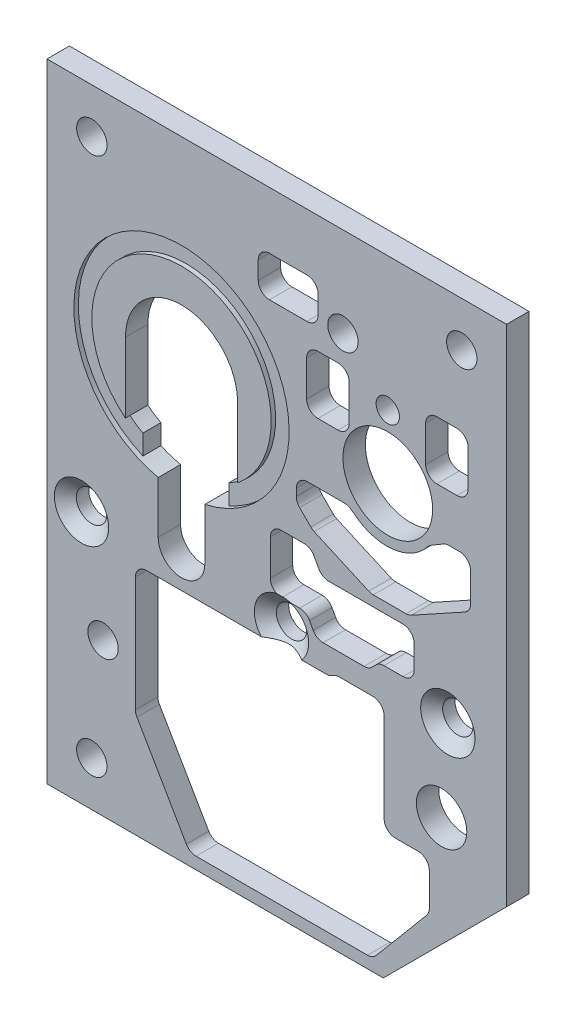
SolidWorks part; units mm, degrees
material "Acrylic (Medium-high impact)"
ref_plane "Front Plane" through (0, 0, 0) normal (0, 0, 1) x (1, 0, 0)
ref_plane "Top Plane" through (0, 0, 0) normal (0, 1, 0) x (1, 0, 0)
ref_plane "Right Plane" through (0, 0, 0) normal (1, 0, 0) x (0, 0, -1)
sketch "Sketch1" plane through (0, 0, 0) normal (0, 0, 1) x (1, 0, 0)
  line L5 (-65.0875, 0) -> (-65.0875, -88.9)
  line L6 (-65.0875, -88.9) -> (-17.4625, -88.9)
  line L7 (-17.4625, -88.9) -> (0, -71.4375)
  line L8 (0, -71.4375) -> (0, 0)
  line L9 (0, 0) -> (-65.0875, 0)
  line L10 (-65.0875, 0) -> (-65.0875, -88.9)
  line L11 (-65.0875, -88.9) -> (-17.4625, -88.9)
  line L12 (-17.4625, -88.9) -> (0, -71.4375)
  line L13 (0, -71.4375) -> (0, 0)
  line L14 (0, 0) -> (-65.0875, 0)
  dimension "D1" = 0
extrude "Boss-Extrude1" add sketch "Sketch1" against normal blind 3.175
hole_wizard "#6 Clearance Hole1" positions "Sketch3" profile "Sketch2" hole size "#6" standard "ANSI Inch" end condition through all
sketch "Sketch3" plane through (0, 0, 0) normal (0, 0, 1) x (1, 0, 0)
  point P0 (-58.7375, -6.35)
  point P3 (-6.35, -6.35)
  point P6 (-23.1775, -12.7)
  point P9 (-57.15, -67.31)
  point P12 (-58.7375, -82.55)
sketch "Sketch2" plane through (-58.7375, -6.35, 0) normal (1, 0, 0) x (0, -1, 0)
  line L0 (0, 0) -> (0, 3.175)
  line L1 (0, 3.175) -> (2.1526, 3.175)
  line L2 (2.1526, 3.175) -> (2.1526, 0)
  line L5 (2.1526, 0) -> (0, 0)
  line L11 (0, -6.35) -> (0, 107.95) construction
  dimension "Thru Hole Dia." = 4.3053
  dimension "Thru Hole Depth" = 3.175
sketch "Sketch4" plane through (0, 0, 0) normal (0, 0, 1) x (1, 0, 0)
  line L0 (-49.3395, -50.8) -> (-49.3395, -43.453) construction
  line L1 (-42.7355, -43.453) -> (-42.7355, -50.8) construction
  line L2 (-49.3395, -50.8) -> (-49.3395, -43.453)
  line L3 (-42.7355, -43.453) -> (-42.7355, -50.8)
  arc A0 (-42.7355, -43.453) -> (-49.3395, -43.453) centre (-46.0375, -28.575) ccw construction
  arc A1 (-49.3395, -50.8) -> (-42.7355, -50.8) centre (-46.0375, -50.8) ccw construction
  arc A2 (-42.7355, -43.453) -> (-49.3395, -43.453) centre (-46.0375, -28.575) ccw
  arc A3 (-49.3395, -50.8) -> (-42.7355, -50.8) centre (-46.0375, -50.8) ccw
extrude "Cut-Extrude1" cut sketch "Sketch4" against normal through all
sketch "Sketch5" plane through (0, 0, 0) normal (0, 0, 1) x (1, 0, 0)
  circle A0 centre (-16.8275, -27.94) radius 6.35
  circle A1 centre (-16.8275, -18.9484) radius 1.651
  dimension "D1" = 12.7
  dimension "D2" = 3.302
  dimension "D3" = 8.9916
extrude "Cut-Extrude2" cut sketch "Sketch5" against normal through all
hole_wizard "1/4 Clearance Hole1" positions "Sketch7" profile "Sketch6" hole size "1/4" standard "ANSI Inch" end condition through all
sketch "Sketch7" plane through (0, 0, 0) normal (0, 0, 1) x (1, 0, 0)
  point P0 (-9.2075, -65.0875)
sketch "Sketch6" plane through (-9.2075, -65.0875, 0) normal (1, 0, 0) x (0, -1, 0)
  line L0 (0, 0) -> (0, 3.175)
  line L1 (0, 3.175) -> (3.5712, 3.175)
  line L2 (3.5712, 3.175) -> (3.5712, 0)
  line L5 (3.5712, 0) -> (0, 0)
  line L11 (0, -6.35) -> (0, 107.95) construction
  dimension "Thru Hole Dia." = 7.1425
  dimension "Thru Hole Depth" = 3.175
sketch "Sketch8" plane through (0, 0, -3.175) normal (0, 0, -1) x (-1, 0, 0)
  line L0 (52.1335, -39.7163) -> (52.1335, -42.5427) construction
  line L1 (53.975, -28.575) -> (53.975, -38.4889) construction
  line L2 (38.1, -38.4889) -> (38.1, -28.575) construction
  line L3 (39.9415, -42.5427) -> (39.9415, -39.7163) construction
  line L4 (52.1335, -39.7163) -> (52.1335, -42.5427)
  line L5 (53.975, -28.575) -> (53.975, -38.4889)
  line L6 (38.1, -38.4889) -> (38.1, -28.575)
  line L7 (39.9415, -42.5427) -> (39.9415, -39.7163)
  arc A0 (52.1335, -39.7163) -> (53.975, -38.4889) centre (46.0375, -28.575) ccw construction
  arc A1 (53.975, -28.575) -> (38.1, -28.575) centre (46.0375, -28.575) ccw construction
  arc A2 (38.1, -38.4889) -> (39.9415, -39.7163) centre (46.0375, -28.575) ccw construction
  arc A3 (49.3395, -43.453) -> (42.7355, -43.453) centre (46.0375, -28.575) ccw construction
  arc A4 (52.1335, -39.7163) -> (53.975, -38.4889) centre (46.0375, -28.575) ccw
  arc A5 (53.975, -28.575) -> (38.1, -28.575) centre (46.0375, -28.575) ccw
  arc A6 (38.1, -38.4889) -> (39.9415, -39.7163) centre (46.0375, -28.575) ccw
  arc A7 (52.1335, -42.5427) -> (39.9415, -42.5427) centre (46.0375, -28.575) ccw
extrude "Boss-Extrude2" add sketch "Sketch8" against normal through all
sketch "Sketch9" plane through (0, 0, 0) normal (0, 0, 1) x (1, 0, 0)
  line L0 (-52.1335, -39.7163) -> (-52.1335, -42.5427) construction
  line L1 (-39.9415, -42.5427) -> (-39.9415, -39.7163) construction
  line L2 (-52.1335, -39.7163) -> (-52.1335, -42.5427)
  line L3 (-39.9415, -42.5427) -> (-39.9415, -39.7163)
  arc A0 (-42.7355, -43.453) -> (-49.3395, -43.453) centre (-46.0375, -28.575) ccw construction
  arc A1 (-53.975, -38.4889) -> (-52.1335, -39.7163) centre (-46.0375, -28.575) ccw construction
  arc A2 (-38.1, -38.4889) -> (-53.975, -38.4889) centre (-46.0375, -28.575) ccw construction
  arc A3 (-39.9415, -39.7163) -> (-38.1, -38.4889) centre (-46.0375, -28.575) ccw construction
  arc A4 (-39.9415, -42.5427) -> (-52.1335, -42.5427) centre (-46.0375, -28.575) ccw
  arc A5 (-53.975, -38.4889) -> (-52.1335, -39.7163) centre (-46.0375, -28.575) ccw
  arc A6 (-38.1, -38.4889) -> (-53.975, -38.4889) centre (-46.0375, -28.575) ccw
  arc A7 (-39.9415, -39.7163) -> (-38.1, -38.4889) centre (-46.0375, -28.575) ccw
extrude "Cut-Extrude3" cut sketch "Sketch9" against normal blind 0.635
hole_wizard "CSK for #6 Flat Head Machine Screw (100)1" positions "Sketch11" profile "Sketch10" countersink size "#6" standard "ANSI Inch" end condition through all
sketch "Sketch11" plane through (0, 0, 0) normal (0, 0, 1) x (1, 0, 0)
  point P1 (-31.877, -53.0919)
  point P5 (-60.198, -53.0919)
  point P8 (-8.321, -53.0919)
sketch "Sketch10" plane through (-31.877, -53.0919, 0) normal (1, 0, 0) x (0, -1, 0)
  line L0 (0, 0) -> (0, 3.175)
  line L1 (0, 3.175) -> (2.1526, 3.175)
  line L2 (2.1526, 3.175) -> (2.1526, 1.4209)
  line L3 (2.1526, 1.4209) -> (3.846, 0)
  line L5 (3.846, 0) -> (0, 0)
  line L6 (-2.1526, 1.4209) -> (-3.846, 0) construction
  line L11 (0, -6.35) -> (0, 107.95) construction
  dimension "Thru Hole Dia." = 4.3053
  dimension "Thru Hole Depth" = 3.175
  dimension "Near C'Sink Dia." = 7.692
  dimension "Near C'Sink Angle" = 100
sketch "Sketch13" plane through (0, 0, 0) normal (0, 0, 1) x (1, 0, 0)
  line L0 (-33.5834, -8.0877) -> (-28.2715, -8.0877)
  line L1 (-26.684, -9.6752) -> (-26.684, -12.1963)
  line L2 (-28.2715, -13.7838) -> (-33.5834, -13.7838)
  line L3 (-35.1709, -9.6752) -> (-35.1709, -12.1963)
  line L4 (-9.8743, -16.2715) -> (-7.0294, -16.2715)
  line L5 (-5.4419, -17.859) -> (-5.4419, -22.9231)
  line L6 (-7.0294, -24.5106) -> (-9.8743, -24.5106)
  line L7 (-11.4618, -22.9231) -> (-11.4618, -17.859)
  line L8 (-26.728, -16.6728) -> (-23.8831, -16.6728)
  line L9 (-22.2956, -18.2603) -> (-22.2956, -23.3243)
  line L10 (-23.8831, -24.9118) -> (-26.728, -24.9118)
  line L11 (-28.3155, -23.3243) -> (-28.3155, -18.2603)
  line L17 (-13.0908, -45.6924) -> (-13.0908, -48.9531)
  line L23 (-33.4611, -47.8684) -> (-33.4611, -42.8044)
  line L24 (-29.3162, -37.1302) -> (-27.7292, -38.7172)
  line L25 (-27.2516, -39.0452) -> (-19.5276, -42.4798)
  line L26 (-18.8826, -42.6167) -> (-14.2496, -42.6167)
  line L27 (-13.4825, -42.4191) -> (-5.915, -38.243)
  line L28 (-5.0945, -36.8531) -> (-5.0945, -32.7951)
  line L29 (-6.682, -31.2076) -> (-8.167, -31.2076)
  line L32 (-22.9356, -33.4058) -> (-28.1937, -33.4058)
  line L33 (-29.7812, -34.9933) -> (-29.7812, -36.0077)
  line L34 (-50.973, -55.6802) -> (-25.5623, -55.6802)
  line L37 (-15.7595, -70.8877) -> (-12.5337, -70.8876)
  line L38 (-10.9462, -72.4751) -> (-10.9462, -77.1078)
  line L39 (-11.3183, -78.129) -> (-18.4811, -86.653)
  line L40 (-19.6965, -87.2192) -> (-43.9811, -87.2192)
  line L41 (-45.3548, -86.4273) -> (-52.3467, -74.3556)
  line L42 (-52.5605, -73.56) -> (-52.5605, -57.2677)
  line L43 (-14.6783, -44.1049) -> (-25.206, -44.1049)
  line L44 (-26.5981, -43.2804) -> (-27.2773, -42.0413)
  line L45 (-28.6694, -41.2169) -> (-31.8736, -41.2169)
  line L48 (-25.9975, -52.0435) -> (-20.1851, -52.0435)
  line L49 (-19.0626, -51.5785) -> (-18.4896, -51.0056)
  line L50 (-17.3671, -50.5406) -> (-14.6783, -50.5406)
  line L51 (-27.3896, -51.219) -> (-27.9041, -50.2804)
  line L52 (-29.2962, -49.4559) -> (-31.8736, -49.4559)
  line L54 (-24.662, -55.4002) -> (-24.6221, -55.3728)
  line L55 (-23.7218, -55.0928) -> (-18.9345, -55.0928)
  line L57 (-17.347, -56.6803) -> (-17.347, -69.3002)
  line L58 (-8.9781, -31.4305) -> (-10.7271, -32.4701)
  arc A0 (-28.2715, -8.0877) -> (-26.684, -9.6752) centre (-28.2715, -9.6752) cw
  arc A1 (-26.684, -12.1963) -> (-28.2715, -13.7838) centre (-28.2715, -12.1963) cw
  arc A2 (-33.5834, -13.7838) -> (-35.1709, -12.1963) centre (-33.5834, -12.1963) cw
  arc A3 (-33.5834, -8.0877) -> (-35.1709, -9.6752) centre (-33.5834, -9.6752) ccw
  arc A4 (-5.4419, -22.9231) -> (-7.0294, -24.5106) centre (-7.0294, -22.9231) cw
  arc A5 (-9.8743, -24.5106) -> (-11.4618, -22.9231) centre (-9.8743, -22.9231) cw
  arc A6 (-9.8743, -16.2715) -> (-11.4618, -17.859) centre (-9.8743, -17.859) ccw
  arc A7 (-7.0294, -16.2715) -> (-5.4419, -17.859) centre (-7.0294, -17.859) cw
  arc A8 (-22.2956, -23.3243) -> (-23.8831, -24.9118) centre (-23.8831, -23.3243) cw
  arc A9 (-26.728, -24.9118) -> (-28.3155, -23.3243) centre (-26.728, -23.3243) cw
  arc A10 (-26.728, -16.6728) -> (-28.3155, -18.2603) centre (-26.728, -18.2603) ccw
  arc A11 (-23.8831, -16.6728) -> (-22.2956, -18.2603) centre (-23.8831, -18.2603) cw
  arc A16 (-13.0908, -48.9531) -> (-14.6783, -50.5406) centre (-14.6783, -48.9531) cw
  arc A19 (-14.6783, -44.1049) -> (-13.0908, -45.6924) centre (-14.6783, -45.6924) cw
  arc A21 (-31.8736, -49.4559) -> (-33.4611, -47.8684) centre (-31.8736, -47.8684) cw
  arc A22 (-31.8736, -41.2169) -> (-33.4611, -42.8044) centre (-31.8736, -42.8044) ccw
  arc A24 (-19.5276, -42.4798) -> (-18.8826, -42.6167) centre (-18.8826, -41.0292) ccw
  arc A25 (-14.2496, -42.6167) -> (-13.4825, -42.4191) centre (-14.2496, -41.0292) ccw
  arc A26 (-5.915, -38.243) -> (-5.0945, -36.8531) centre (-6.682, -36.8531) ccw
  arc A27 (-5.0945, -32.7951) -> (-6.682, -31.2076) centre (-6.682, -32.7951) ccw
  arc A31 (-27.7292, -38.7172) -> (-27.2516, -39.0452) centre (-26.6066, -37.5947) ccw
  arc A32 (-29.3162, -37.1302) -> (-29.7812, -36.0077) centre (-28.1937, -36.0077) cw
  arc A33 (-28.1937, -33.4058) -> (-29.7812, -34.9933) centre (-28.1937, -34.9933) ccw
  arc A37 (-12.5337, -70.8876) -> (-10.9462, -72.4751) centre (-12.5337, -72.4751) cw
  arc A38 (-10.9462, -77.1078) -> (-11.3183, -78.129) centre (-12.5337, -77.1078) cw
  arc A39 (-18.4811, -86.653) -> (-19.6965, -87.2192) centre (-19.6965, -85.6317) cw
  arc A40 (-43.9811, -87.2192) -> (-45.3548, -86.4273) centre (-43.9811, -85.6317) cw
  arc A41 (-52.3467, -74.3556) -> (-52.5605, -73.56) centre (-50.973, -73.56) cw
  arc A42 (-50.973, -55.6802) -> (-52.5605, -57.2677) centre (-50.973, -57.2677) ccw
  arc A43 (-27.2773, -42.0413) -> (-28.6694, -41.2169) centre (-28.6694, -42.8044) ccw
  arc A44 (-25.206, -44.1049) -> (-26.5981, -43.2804) centre (-25.206, -42.5174) cw
  arc A45 (-18.4896, -51.0056) -> (-17.3671, -50.5406) centre (-17.3671, -52.1281) cw
  arc A46 (-20.1851, -52.0435) -> (-19.0626, -51.5785) centre (-20.1851, -50.456) ccw
  arc A47 (-27.3896, -51.219) -> (-25.9975, -52.0435) centre (-25.9975, -50.456) ccw
  arc A48 (-27.9041, -50.2804) -> (-29.2962, -49.4559) centre (-29.2962, -51.0434) ccw
  arc A49 (-15.7595, -70.8877) -> (-17.347, -69.3002) centre (-15.7595, -69.3002) cw
  arc A50 (-18.9345, -55.0928) -> (-17.347, -56.6803) centre (-18.9345, -56.6803) cw
  arc A51 (-24.6221, -55.3728) -> (-23.7218, -55.0928) centre (-23.7218, -56.6803) cw
  arc A52 (-24.662, -55.4002) -> (-25.5623, -55.6802) centre (-25.5623, -54.0927) cw
  arc A53 (-11.1669, -32.8573) -> (-21.8769, -33.8104) centre (-16.9676, -28.3255) cw
  arc A54 (-22.9356, -33.4058) -> (-21.8769, -33.8104) centre (-22.9356, -34.9933) cw
  arc A55 (-11.1669, -32.8573) -> (-10.7271, -32.4701) centre (-9.916, -33.8347) cw
  arc A56 (-8.167, -31.2076) -> (-8.9781, -31.4305) centre (-8.167, -32.7951) ccw
  point P127 (0, 0)
  point P128 (0, 0)
  point P129 (-22.7604, -34.9933)
  point P130 (-6.682, -32.7951)
  point P131 (-10.2035, -34.0056)
  dimension "D1" = 1.5875
  dimension "D2" = 1.5875
  dimension "D3" = 1.5875
  dimension "D4" = 1.5875
  dimension "D5" = 1.5875
  dimension "D6" = 1.5875
  dimension "D7" = 1.5875
  dimension "D8" = 1.5875
extrude "Backlighting Holes" cut sketch "Sketch13" against normal through all
